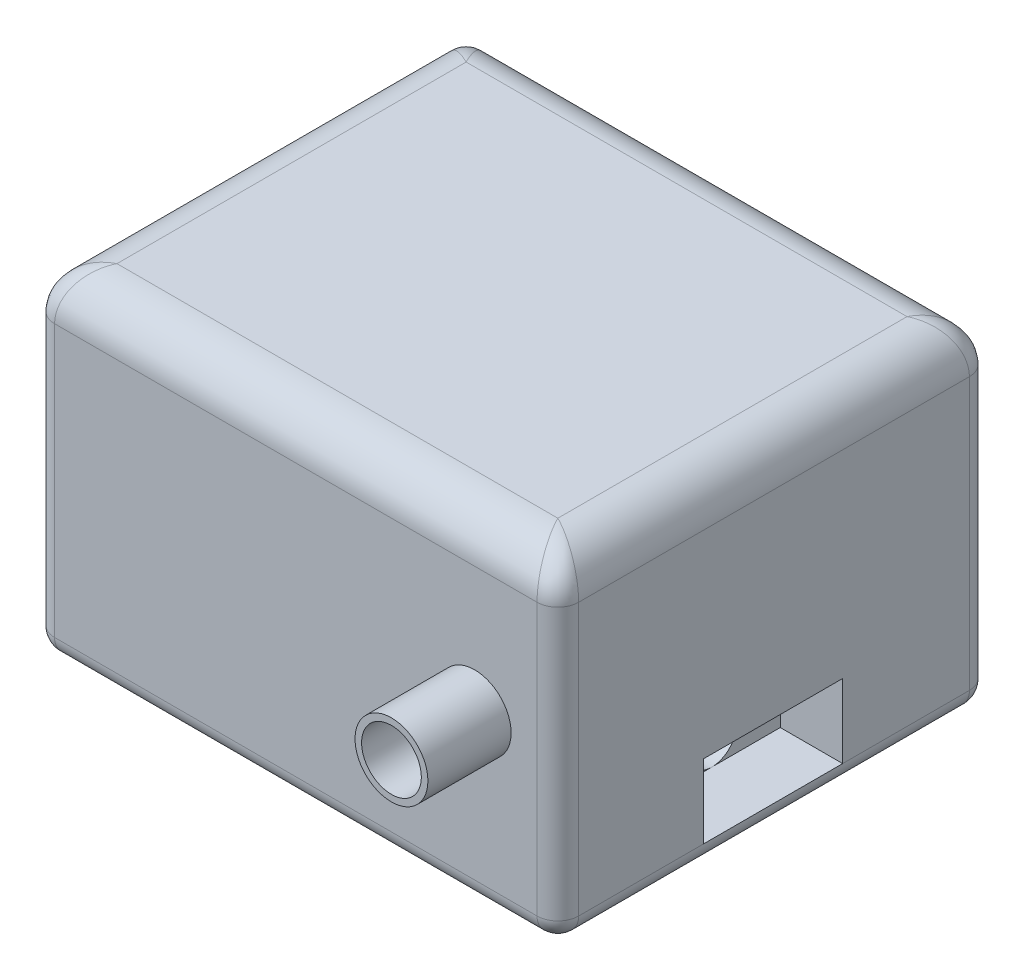
SolidWorks part; units mm, degrees
ref_plane "Front Plane" through (0, 0, 0) normal (0, 0, 1) x (1, 0, 0)
ref_plane "Top Plane" through (0, 0, 0) normal (0, 1, 0) x (1, 0, 0)
ref_plane "Right Plane" through (0, 0, 0) normal (1, 0, 0) x (0, 0, -1)
sketch "Sketch1" plane through (0, 0, 0) normal (0, 0, 1) x (1, 0, 0)
  line L1 (-80, 51) -> (80, 51)
  line L2 (-80, 51) -> (-80, -51)
  line L3 (-80, -51) -> (80, -51)
  line L4 (80, 51) -> (80, -51)
  line L5 (-80, 51) -> (80, -51) construction
  line L6 (-80, -51) -> (80, 51) construction
  point P0 (0, 0)
  dimension "D1" = 160
  dimension "D2" = 102
extrude "Boss-Extrude1" add sketch "Sketch1" along normal mid plane 132
fillet "Fillet1" radius 12.7 4 edges at (80, 51, 0) (0, 51, 66) (-80, 51, 0) (0, 51, -66)
fillet "Fillet2" radius 6.35 12 edges at (76.2803, 47.2803, 62.2803) (76.2803, 47.2803, -62.2803) (-76.2803, 47.2803, -62.2803) (-76.2803, 47.2803, 62.2803) (-80, -51, 0) (0, -51, 66) (80, -51, 0) (80, -6.35, 66) (0, -51, -66) (80, -6.35, -66) (-80, -6.35, -66) (-80, -6.35, 66)
sketch "Sketch2" plane through (0, 0, 66) normal (0, 0, 1) x (1, 0, 0)
  line L0 (73.65, -51) -> (-73.65, -51) construction
  line L2 (80, 38.3) -> (80, -44.65) construction
  circle A0 centre (54.6, -0.2) radius 11.125
  circle A1 centre (54.6, -0.2) radius 9.125
  dimension "D3" = 22.25
  dimension "D4" = 2
  dimension "D1" = 50.8
  dimension "D2" = 25.4
extrude "Boss-Extrude2" add sketch "Sketch2" along normal blind 25.4
sketch "Sketch3" plane through (80, 0, 0) normal (1, 0, 0) x (0, 0, -1)
  line L0 (-59.65, -44.65) -> (59.65, -44.65) construction
  line L1 (-21.55, -44.65) -> (20.95, -44.65)
  line L2 (-21.55, -44.65) -> (-21.55, -22.15)
  line L3 (-21.55, -22.15) -> (20.95, -22.15)
  line L4 (20.95, -44.65) -> (20.95, -22.15)
  line L5 (-66, -44.65) -> (-66, 38.3) construction
  dimension "D1" = 22.5
  dimension "D2" = 42.5
  dimension "D3" = 44.45
extrude "Cut-Extrude1" cut sketch "Sketch3" against normal blind 19.05
sketch "Sketch4" plane through (60.95, 0, 0) normal (1, 0, 0) x (0, 0, -1)
  line L0 (-21.55, -44.65) -> (20.95, -44.65) construction
  line L1 (-21.55, -22.15) -> (-21.55, -44.65) construction
  circle A0 centre (0, -37.03) radius 7.62
  dimension "D1" = 15.24
  dimension "D2" = 21.55
extrude "Cut-Extrude2" cut sketch "Sketch4" against normal blind 19.05
